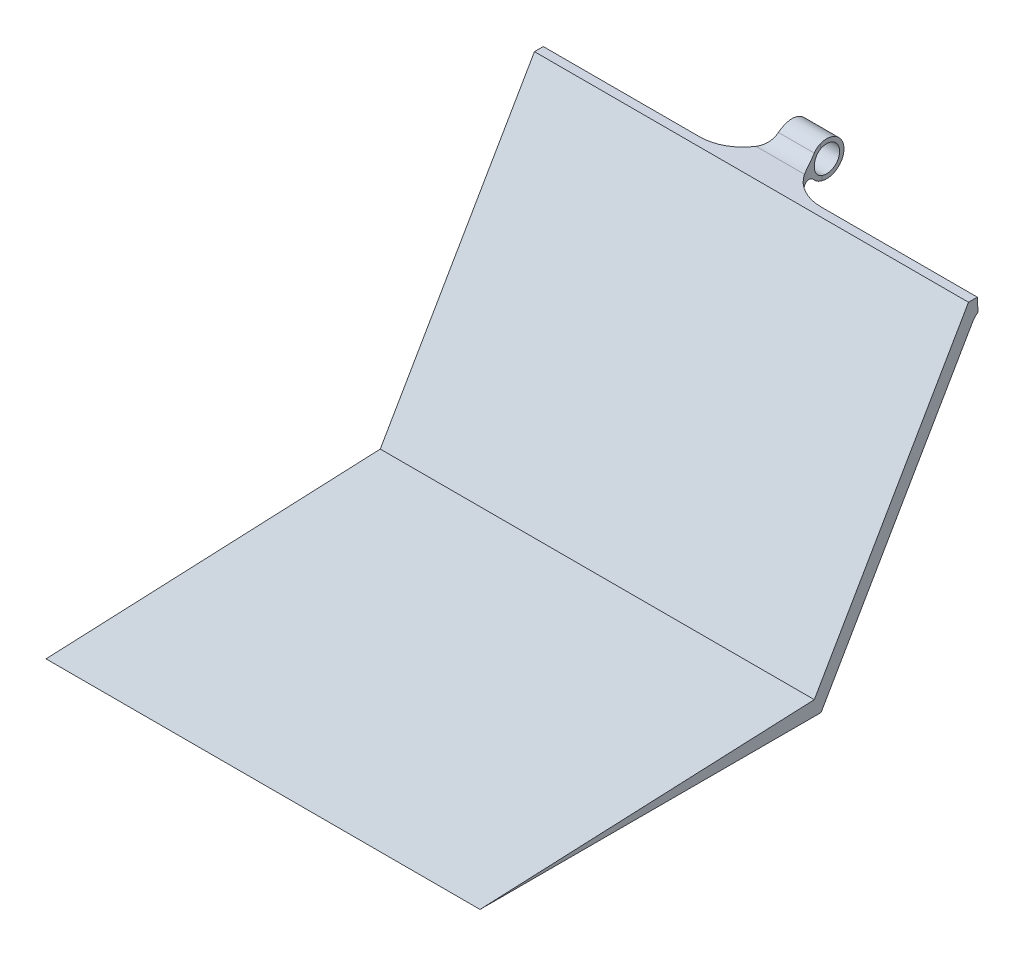
SolidWorks part; units mm, degrees
ref_plane "Front Plane" through (0, 0, 0) normal (0, 0, 1) x (1, 0, 0)
ref_plane "Top Plane" through (0, 0, 0) normal (0, 1, 0) x (1, 0, 0)
ref_plane "Right Plane" through (0, 0, 0) normal (1, 0, 0) x (0, 0, -1)
sketch "Sketch1" plane through (0, 0, 0) normal (1, 0, 0) x (0, 0, -1)
  line L0 (8.9517, 8.4631) -> (1.81, 8.4631)
  line L1 (1.81, 8.4631) -> (-10.5414, -12.9301)
  line L5 (-0.493, 10.5262) -> (8.9517, 10.5262)
  line L6 (-10.5414, -12.9301) -> (-20.4326, -30.0622)
  line L7 (-20.4326, -30.0622) -> (-34.4616, -54.3611)
  line L8 (-34.4616, -54.3611) -> (-113.0291, -54.3611)
  line L9 (-0.493, 10.5262) -> (-36.0181, -51.0051)
  line L11 (-113.0291, -54.3611) -> (-36.0181, -51.0051)
  circle A0 centre (12.8164, 9.4947) radius 3
  arc A1 (8.9517, 8.4631) -> (8.9517, 10.5262) centre (12.8164, 9.4947) ccw
  dimension "D1" = 8
  dimension "D2" = 6
  dimension "D3" = 120
extrude "Boss-Extrude1" add sketch "Sketch1" along normal mid plane 100
sketch "Sketch2" plane through (0, -11.4208, -0.5711) normal (0, 0.9988, 0.0499) x (1, 0, 0)
  line L1 (-41.3457, -80.9764) -> (-37.3457, -80.9764)
  line L2 (-41.3457, -80.9764) -> (-41.3457, -96.6429)
  line L4 (-37.3457, -80.9764) -> (-37.3457, -96.6429)
  line L6 (-49.3457, -96.6429) -> (-45.6823, -102.6216)
  line L8 (-45.6823, -102.6216) -> (-41.3457, -96.6429)
  line L9 (-49.3457, -96.6429) -> (-36.6452, -96.6429) construction
  line L10 (-37.3457, -96.6429) -> (-33.6823, -102.6216)
  line L11 (-33.6823, -102.6216) -> (-29.3457, -96.6429)
  line L12 (-29.3457, -80.9764) -> (-29.3457, -96.6429)
  line L13 (-25.3457, -80.9764) -> (-25.3457, -96.6429)
  line L14 (-29.3457, -80.9764) -> (-25.3457, -80.9764)
  line L15 (-25.3457, -96.6429) -> (-21.6823, -102.6216)
  line L16 (-21.6823, -102.6216) -> (-17.3457, -96.6429)
  line L17 (-17.3457, -80.9764) -> (-17.3457, -96.6429)
  line L18 (-13.3457, -80.9764) -> (-13.3457, -96.6429)
  line L19 (-17.3457, -80.9764) -> (-13.3457, -80.9764)
  line L20 (-13.3457, -96.6429) -> (-9.6823, -102.6216)
  line L21 (-9.6823, -102.6216) -> (-5.3457, -96.6429)
  line L22 (-5.3457, -80.9764) -> (-5.3457, -96.6429)
  line L23 (-1.3457, -80.9764) -> (-1.3457, -96.6429)
  line L24 (-5.3457, -80.9764) -> (-1.3457, -80.9764)
  line L25 (-1.3457, -96.6429) -> (2.3177, -102.6216)
  line L26 (2.3177, -102.6216) -> (6.6543, -96.6429)
  line L27 (6.6543, -80.9764) -> (6.6543, -96.6429)
  line L28 (10.6543, -80.9764) -> (10.6543, -96.6429)
  line L29 (6.6543, -80.9764) -> (10.6543, -80.9764)
  line L30 (10.6543, -96.6429) -> (14.3177, -102.6216)
  line L31 (14.3177, -102.6216) -> (18.6543, -96.6429)
  line L32 (18.6543, -80.9764) -> (18.6543, -96.6429)
  line L33 (22.6543, -80.9764) -> (22.6543, -96.6429)
  line L34 (18.6543, -80.9764) -> (22.6543, -80.9764)
  line L35 (22.6543, -96.6429) -> (26.3177, -102.6216)
  line L36 (26.3177, -102.6216) -> (30.6543, -96.6429)
  line L37 (30.6543, -80.9764) -> (30.6543, -96.6429)
  line L38 (34.6543, -80.9764) -> (34.6543, -96.6429)
  line L39 (30.6543, -80.9764) -> (34.6543, -80.9764)
  line L40 (34.6543, -96.6429) -> (38.3177, -102.6216)
  line L41 (38.3177, -102.6216) -> (42.6543, -96.6429)
  line L42 (42.6543, -80.9764) -> (42.6543, -96.6429)
  line L43 (46.6543, -80.9764) -> (46.6543, -96.6429)
  line L44 (42.6543, -80.9764) -> (46.6543, -80.9764)
  line L45 (46.6543, -96.6429) -> (50.3177, -102.6216)
  line L46 (50.3177, -102.6216) -> (54.6543, -96.6429)
  line L47 (54.6543, -80.9764) -> (54.6543, -96.6429)
  line L48 (58.6543, -80.9764) -> (58.6543, -96.6429)
  line L49 (54.6543, -80.9764) -> (58.6543, -80.9764)
  line L50 (-49.3457, -96.6429) -> (-58.3428, -96.6429)
  line L51 (-58.3428, -96.6429) -> (-58.3428, -117.6475)
  line L52 (-58.3428, -117.6475) -> (58.6543, -117.6475)
  line L53 (58.6543, -117.6475) -> (58.6543, -96.6429)
  line L54 (0, 0) -> (0, 23.1084) construction
  line L55 (50, 2.0679) -> (-50, 2.0679) construction
  line L56 (-53.2376, 22.2338) -> (-4, 22.2338)
  line L57 (-53.2376, 22.2338) -> (-53.2376, 2.0679)
  line L58 (-53.2376, 2.0679) -> (-4, 2.0679)
  line L59 (-4, 22.2338) -> (-4, 2.0679)
  line L60 (4, 22.2338) -> (4, 2.0679)
  line L61 (53.2376, 2.0679) -> (4, 2.0679)
  line L62 (53.2376, 22.2338) -> (53.2376, 2.0679)
  line L63 (53.2376, 22.2338) -> (4, 22.2338)
  dimension "D1" = 8
  dimension "D2" = 4
  dimension "D4" = 4
  dimension "D3" = 9
extrude "Cut-Extrude1" cut sketch "Sketch2" against normal mid plane 70
fillet "Fillet1" radius 10 2 edges at (-4, 9.365, -1.6021) (4, 9.365, -1.6021)
fillet "Fillet3" radius 5 1 edges at (0, 8.4631, -1.81)
fillet "Fillet4" radius 5 2 edges at (0, 8.4631, -8.9517) (0, 10.5262, -8.9517)
